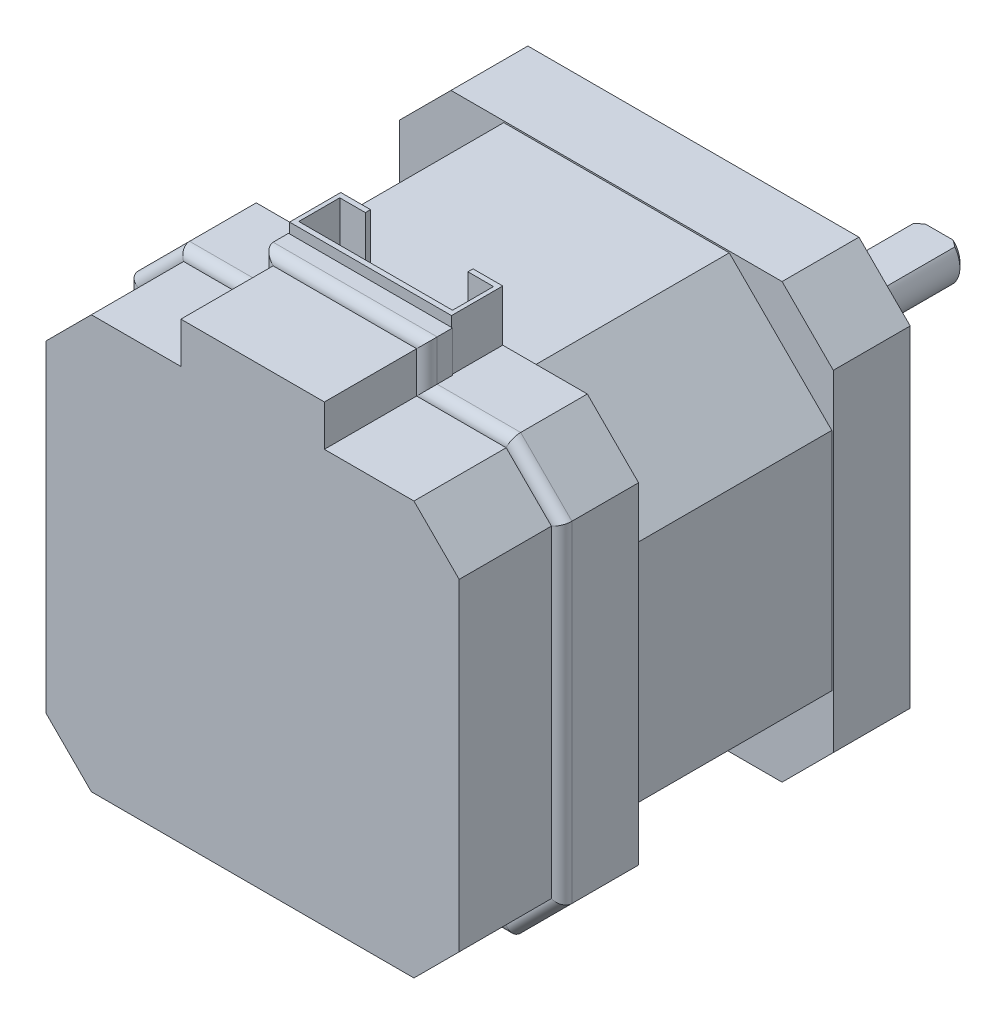
SolidWorks part; units mm, degrees
ref_plane "前视基准面" through (0, 0, 0) normal (0, 0, 1) x (1, 0, 0)
ref_plane "上视基准面" through (0, 0, 0) normal (0, 1, 0) x (1, 0, 0)
ref_plane "右视基准面" through (0, 0, 0) normal (1, 0, 0) x (0, 0, -1)
sketch "草图1" plane through (0, 0, 0) normal (0, 0, 1) x (1, 0, 0)
  line L1 (-21, 21) -> (21, 21)
  line L2 (-21, 21) -> (-21, -21)
  line L3 (-21, -21) -> (21, -21)
  line L4 (21, 21) -> (21, -21)
  line L5 (-21, 21) -> (21, -21) construction
  line L6 (-21, -21) -> (21, 21) construction
  line L11 (-15.5, 15.5) -> (15.5, -15.5) construction
  line L12 (-15.5, -15.5) -> (15.5, 15.5) construction
  point P0 (0, 0)
  point P5 (0, 0)
  dimension "D1" = 42
  dimension "D2" = 42
extrude "凸台-拉伸1" add sketch "草图1" along normal blind 19
chamfer "倒角1" distance 10 angle 45 4 edges at (-21, -21, 9.5) (21, -21, 9.5) (21, 21, 9.5) (-21, 21, 9.5)
sketch "草图2" plane through (0, 0, 19) normal (0, 0, 1) x (1, 0, 0)
  line L1 (-21.15, 21.15) -> (21.15, 21.15)
  line L2 (-21.15, 21.15) -> (-21.15, -21.15)
  line L3 (-21.15, -21.15) -> (21.15, -21.15)
  line L4 (21.15, 21.15) -> (21.15, -21.15)
  line L5 (-21.15, 21.15) -> (21.15, -21.15) construction
  line L6 (-21.15, -21.15) -> (21.15, 21.15) construction
  point P0 (0, 0)
  dimension "D1" = 42.3
  dimension "D2" = 42.3
extrude "凸台-拉伸2" add sketch "草图2" along normal blind 7.5
sketch "草图3" plane through (0, 0, 0) normal (0, 0, -1) x (-1, 0, 0)
  line L5 (-21.15, 21.15) -> (21.15, 21.15)
  line L6 (-21.15, 21.15) -> (-21.15, -21.15)
  line L7 (-21.15, -21.15) -> (21.15, -21.15)
  line L8 (21.15, 21.15) -> (21.15, -21.15)
  line L9 (-21.15, 21.15) -> (21.15, -21.15) construction
  line L10 (-21.15, -21.15) -> (21.15, 21.15) construction
  point P0 (0, 0)
  point P1 (0, 0)
extrude "凸台-拉伸3" add sketch "草图3" along normal blind 7.5
chamfer "倒角2" distance 5 angle 45 8 edges at (-21.15, -21.15, -3.75) (-21.15, -21.15, 22.75) (21.15, -21.15, 22.75) (21.15, -21.15, -3.75) (21.15, 21.15, -3.75) (21.15, 21.15, 22.75) (-21.15, 21.15, 22.75) (-21.15, 21.15, -3.75)
sketch "草图4" plane through (0, 0, -7.5) normal (0, 0, -1) x (-1, 0, 0)
  line L1 (-15.5, 15.5) -> (15.5, 15.5) construction
  line L2 (-15.5, 15.5) -> (-15.5, -15.5) construction
  line L3 (-15.5, -15.5) -> (15.5, -15.5) construction
  line L4 (15.5, 15.5) -> (15.5, -15.5) construction
  line L5 (-15.5, 15.5) -> (15.5, -15.5) construction
  line L6 (-15.5, -15.5) -> (15.5, 15.5) construction
  circle A0 centre (-15.5, 15.5) radius 1.5
  circle A1 centre (15.5, 15.5) radius 1.5
  circle A2 centre (15.5, -15.5) radius 1.5
  circle A3 centre (-15.5, -15.5) radius 1.5
  point P0 (0, 0)
extrude "切除-拉伸1" cut sketch "草图4" against normal blind 4.5
sketch "草图5" plane through (0, 0, -7.5) normal (0, 0, -1) x (-1, 0, 0)
  circle A0 centre (0, 0) radius 11
  circle A1 centre (0, 0) radius 3.75
extrude "凸台-拉伸4" add sketch "草图5" along normal blind 2
sketch "草图6" plane through (0, 0, -7.5) normal (0, 0, -1) x (-1, 0, 0)
  circle A0 centre (0, 0) radius 2.5
extrude "凸台-拉伸5" add sketch "草图6" along normal blind 24
sketch "草图7" plane through (0, 0, -31.5) normal (0, 0, -1) x (-1, 0, 0)
  line L3 (2, 1.5) -> (-2, 1.5)
  arc A0 (2, 1.5) -> (-2, 1.5) centre (0, 0) ccw
extrude "切除-拉伸2" cut sketch "草图7" against normal blind 19
chamfer "倒角3" distance 0.5 angle 45 1 edges at (0, -2.5, -31.5)
sketch "草图8" plane through (0, 0, 26.5) normal (0, 0, 1) x (1, 0, 0)
  line L0 (0, 21.15) -> (-8, 21.15)
  line L1 (16.15, 21.15) -> (-16.15, 21.15) construction
  line L2 (-8, 21.15) -> (-8, 25.15)
  line L3 (-8, 25.15) -> (8, 25.15)
  line L4 (8, 25.15) -> (8, 21.15)
  line L5 (8, 21.15) -> (0, 21.15)
extrude "凸台-拉伸6" add sketch "草图8" against normal blind 2.5
fillet "圆角1" radius 1 12 edges at (-18.65, 18.65, 26.5) (-12.075, 21.15, 26.5) (-8, 23.15, 26.5) (0, 25.15, 26.5) (8, 23.15, 26.5) (12.075, 21.15, 26.5) (18.65, 18.65, 26.5) (21.15, 0, 26.5) (18.65, -18.65, 26.5) (0, -21.15, 26.5) (-18.65, -18.65, 26.5) (-21.15, 0, 26.5)
sketch "草图9" plane through (0, 21.15, 0) normal (0, 1, 0) x (1, 0, 0)
  line L5 (7.9, -19) -> (5, -19)
  line L6 (-7.9, -24) -> (7.9, -24)
  line L7 (-7.5, -23.5) -> (-7.5, -19.5)
  line L8 (7.5, -19.5) -> (5, -19.5)
  line L9 (7.5, -23.5) -> (7.5, -19.5)
  line L10 (-7.5, -23.5) -> (7.5, -23.5)
  line L13 (-5, -19) -> (-5, -19.5)
  line L14 (5, -19) -> (5, -19.5)
  line L15 (-5, -19) -> (-7.9, -19)
  line L16 (8, -19) -> (-8, -19) construction
  line L17 (-5, -19.5) -> (-7.5, -19.5)
  line L18 (7.5, -19.5) -> (-7.5, -19.5) construction
  line L19 (-8, -24) -> (8, -24) construction
  line L20 (-7.9, -19) -> (-7.9, -24)
  line L21 (8, -24) -> (-8, -24) construction
  line L22 (-8, -24) -> (-8, -19) construction
  line L23 (7.9, -19) -> (7.9, -24)
  line L25 (8, -24) -> (8, -19) construction
  dimension "D1" = 0.5
extrude "凸台-拉伸7" add sketch "草图9" along normal blind 5
sketch "草图10" plane through (0, 0, 26.5) normal (0, 0, 1) x (1, 0, 0)
  line L12 (-7, 20.15) -> (-15.7358, 20.15)
  line L13 (-15.7358, 20.15) -> (-20.15, 15.7358)
  line L14 (-20.15, 15.7358) -> (-20.15, -15.7358)
  line L15 (-20.15, -15.7358) -> (-15.7358, -20.15)
  line L16 (-15.7358, -20.15) -> (15.7358, -20.15)
  line L17 (15.7358, -20.15) -> (20.15, -15.7358)
  line L18 (20.15, -15.7358) -> (20.15, 15.7358)
  line L19 (20.15, 15.7358) -> (15.7358, 20.15)
  line L20 (15.7358, 20.15) -> (7, 20.15)
  line L21 (7, 20.15) -> (7, 24.15)
  line L22 (7, 24.15) -> (-7, 24.15)
  line L23 (-7, 24.15) -> (-7, 20.15)
  line L24 (-7, 20.15) -> (-15.7358, 20.15)
  line L25 (-15.7358, 20.15) -> (-20.15, 15.7358)
  line L26 (-20.15, 15.7358) -> (-20.15, -15.7358)
  line L27 (-20.15, -15.7358) -> (-15.7358, -20.15)
  line L28 (-15.7358, -20.15) -> (15.7358, -20.15)
  line L29 (15.7358, -20.15) -> (20.15, -15.7358)
  line L30 (20.15, -15.7358) -> (20.15, 15.7358)
  line L31 (20.15, 15.7358) -> (15.7358, 20.15)
  line L32 (15.7358, 20.15) -> (7, 20.15)
  line L33 (7, 20.15) -> (7, 24.15)
  line L34 (7, 24.15) -> (-7, 24.15)
  line L35 (-7, 24.15) -> (-7, 20.15)
  dimension "D1" = 0
extrude "凸台-拉伸8" add sketch "草图10" along normal blind 9
chamfer "倒角4" distance 2.5 angle 45 1 edges at (-2.5, 0, -7.5)
